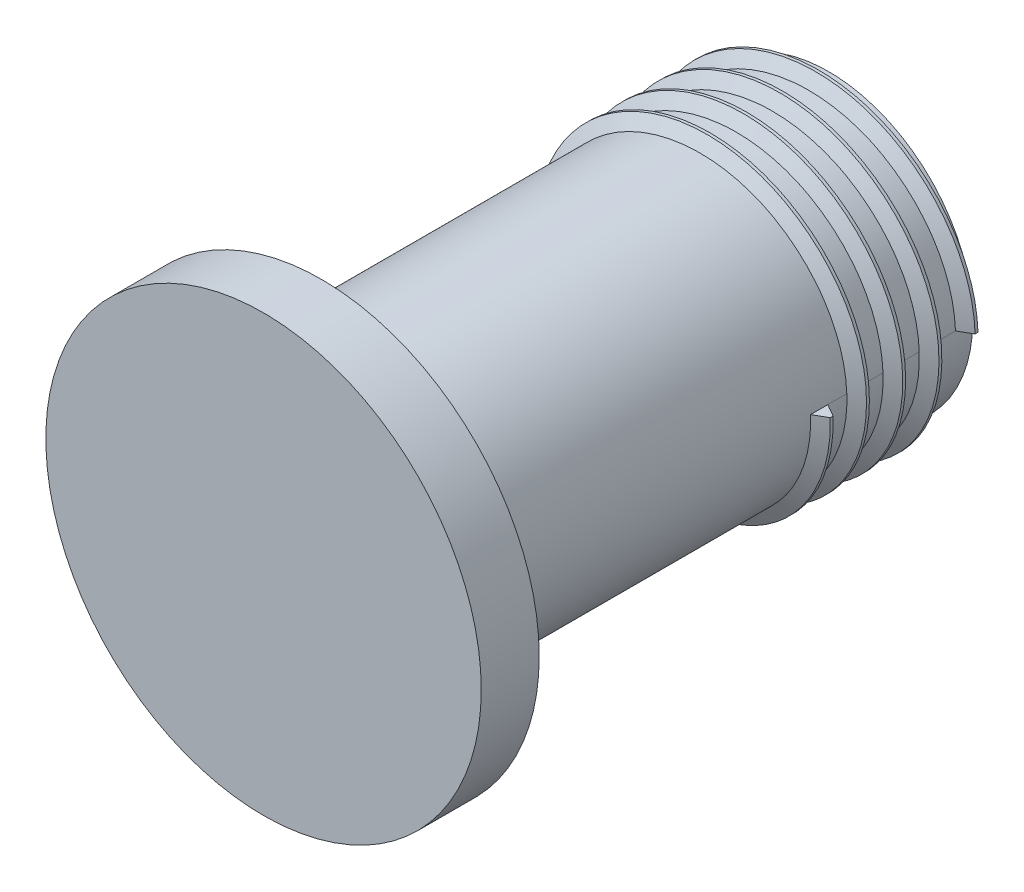
SolidWorks part; units mm, degrees
ref_plane "前基準面" through (0, 0, 0) normal (0, 0, 1) x (1, 0, 0)
ref_plane "上基準面" through (0, 0, 0) normal (0, 1, 0) x (1, 0, 0)
ref_plane "右基準面" through (0, 0, 0) normal (1, 0, 0) x (0, 0, -1)
sketch "草圖1" plane through (0, 0, 0) normal (0, 0, 1) x (1, 0, 0)
  circle A0 centre (0, 0) radius 3.0043
extrude "填料-伸長1" add sketch "草圖1" along normal blind 0.8
sketch "草圖2" plane through (0, 0, 0) normal (0, 0, -1) x (-1, 0, 0)
  circle A0 centre (0, 0) radius 1.9868
extrude "填料-伸長2" add sketch "草圖2" along normal blind 7
thread "螺紋2" pitch 0.3175 method extrude profile "螺紋輪廓4" start angle 0, offset 0, length 2, pitch 0.5, diameter 3.9736
ref_plane "平面4" through (1.9868, 0, -7) normal (0, -1, 0) x (1, 0, 0)
sketch "螺紋輪廓4" plane through (1.9868, 0, -7) normal (0, -1, 0) x (1, 0, 0)
  line L0 (0, 0) -> (0, 0.3175) construction
  line L1 (0, 0) -> (0.1719, 0.0992)
  line L2 (0.1719, 0.0992) -> (0.1719, 0.1389)
  line L3 (0.1719, 0.1389) -> (0, 0.2381)
  line L4 (0.1719, 0.1191) -> (0, 0.1191) construction
  line L11 (0, 0) -> (0, 0.2381)
  point P2 (0, 0)
  dimension "Pitch" = 0.3175
  dimension "Profile_Angle" = 60
  dimension "Profile_Land" = 0.0397
  dimension "Profile_Height" = 0.1719
